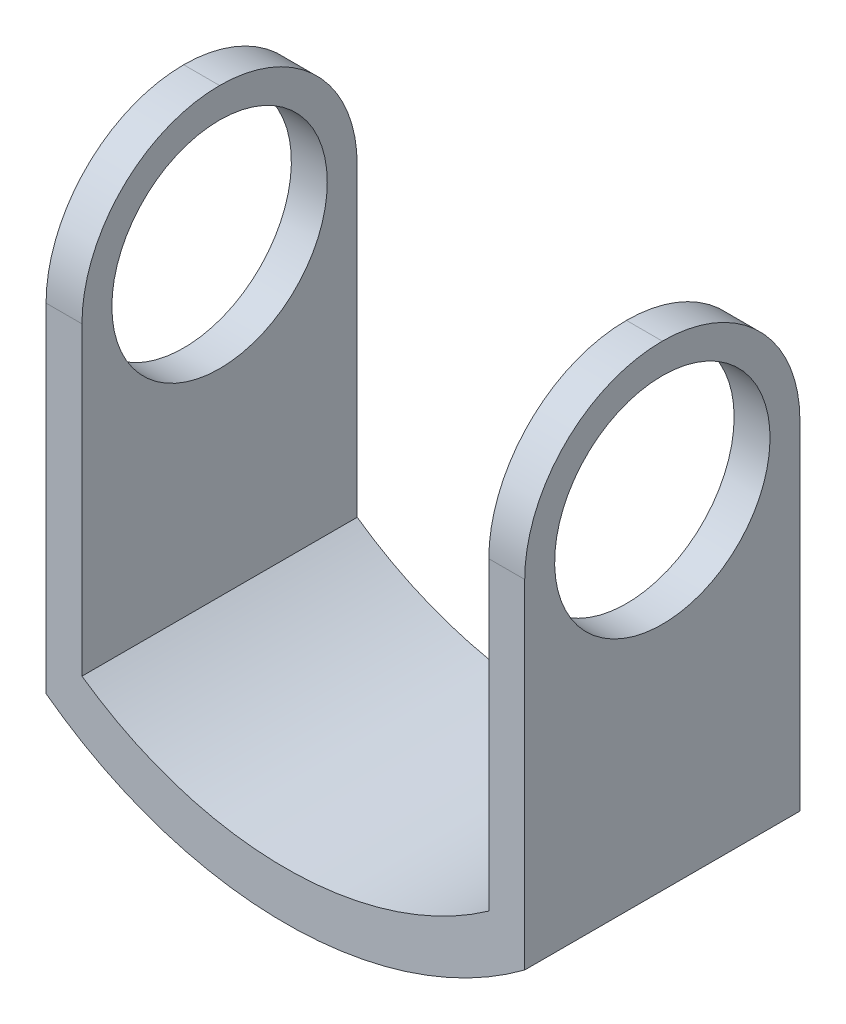
SolidWorks part; units mm, degrees
ref_plane "Plan de face" through (0, 0, 0) normal (0, 0, 1) x (1, 0, 0)
ref_plane "Plan de dessus" through (0, 0, 0) normal (0, 1, 0) x (1, 0, 0)
ref_plane "Plan de droite" through (0, 0, 0) normal (1, 0, 0) x (0, 0, -1)
sketch "Esquisse1" plane through (0, 0, 0) normal (0, 0, 1) x (1, 0, 0)
  line L0 (-10, 0) -> (-8.5, 0)
  line L3 (8.5, 0) -> (10, 0)
  line L4 (10, 0) -> (10, -19.8828)
  line L5 (-10, 0) -> (-10, -19.8828)
  line L6 (-8.5, -18.5) -> (-8.5, 0)
  line L7 (8.5, -18.5) -> (8.5, 0)
  line L8 (0, -21.1954) -> (0, -23.1954) construction
  line L9 (-8.5, 0) -> (8.5, 0) construction
  line L10 (8.5, -6.4454) -> (-8.5, -6.4454) construction
  arc A0 (-8.5, -18.5) -> (8.5, -18.5) centre (0, -6.4454) ccw
  arc A1 (-10, -19.8828) -> (10, -19.8828) centre (0, -6.4454) ccw
  point P12 (0, 0)
  dimension "D3" = 14.75
  dimension "D1" = 1.5
  dimension "D2" = 17
  dimension "D4" = 18.5
  dimension "D5" = 2
extrude "Boss.-Extru.1" add sketch "Esquisse1" along normal blind 11.5
sketch "Esquisse3" plane through (10, 0, 0) normal (1, 0, 0) x (0, 0, -1)
  line L0 (-11.5, 0) -> (0, 0) construction
  circle A0 centre (-5.75, -5.75) radius 4.5
  point P5 (-5.75, 0)
  dimension "D1" = 9
  dimension "D2" = 5.75
extrude "Enlèv. mat.-Extru.1" cut sketch "Esquisse3" against normal up to surface (20 mm away) up to face at (-10, -9.9414, 5.75)
fillet "Congé1" radius 5.75 4 edges at (-9.25, 0, 0) (-9.25, 0, 11.5) (9.25, 0, 0) (9.25, 0, 11.5)
